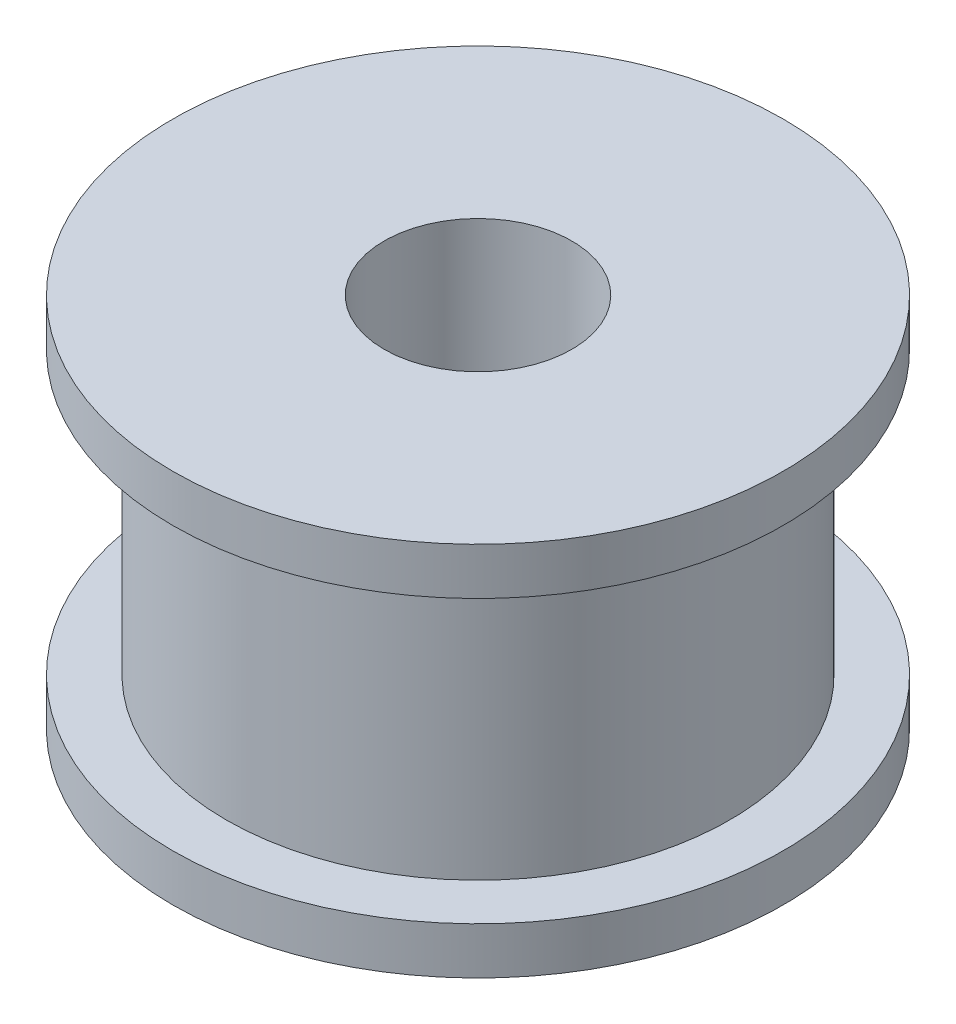
SolidWorks part; units mm, degrees
material "AISI 304"
ref_plane "前视基准面" through (0, 0, 0) normal (0, 0, 1) x (1, 0, 0)
ref_plane "上视基准面" through (0, 0, 0) normal (0, 1, 0) x (1, 0, 0)
ref_plane "右视基准面" through (0, 0, 0) normal (1, 0, 0) x (0, 0, -1)
sketch "Sketch1" plane through (0, 0, 0) normal (0, 1, 0) x (1, 0, 0)
  circle A0 centre (0, 0) radius 10.725
  dimension "D1" = 21.45
extrude "Boss-Extrude1" add sketch "Sketch1" along normal mid plane 12
sketch "Sketch2" plane through (0, 0, 0) normal (0, 1, 0) x (1, 0, 0)
  circle A0 centre (0, 0) radius 13
  dimension "D1" = 26
extrude "Boss-Extrude2" add sketch "Sketch2" along normal blind 2 from surface starting at face at (0, 6, 10.725)
extrude "Boss-Extrude3" add sketch "Sketch2<2>" against normal blind 2 from surface starting at face at (0, -6, 10.725)
sketch "Sketch2<2>" plane through (0, 0, 0) normal (0, 1, 0) x (1, 0, 0) same geometry as "Sketch2"
sketch "Sketch3" plane through (0, 8, 0) normal (0, 1, 0) x (1, 0, 0)
  circle A0 centre (0, 0) radius 4
  dimension "D1" = 8
extrude "Cut-Extrude1" cut sketch "Sketch3" against normal up to next
